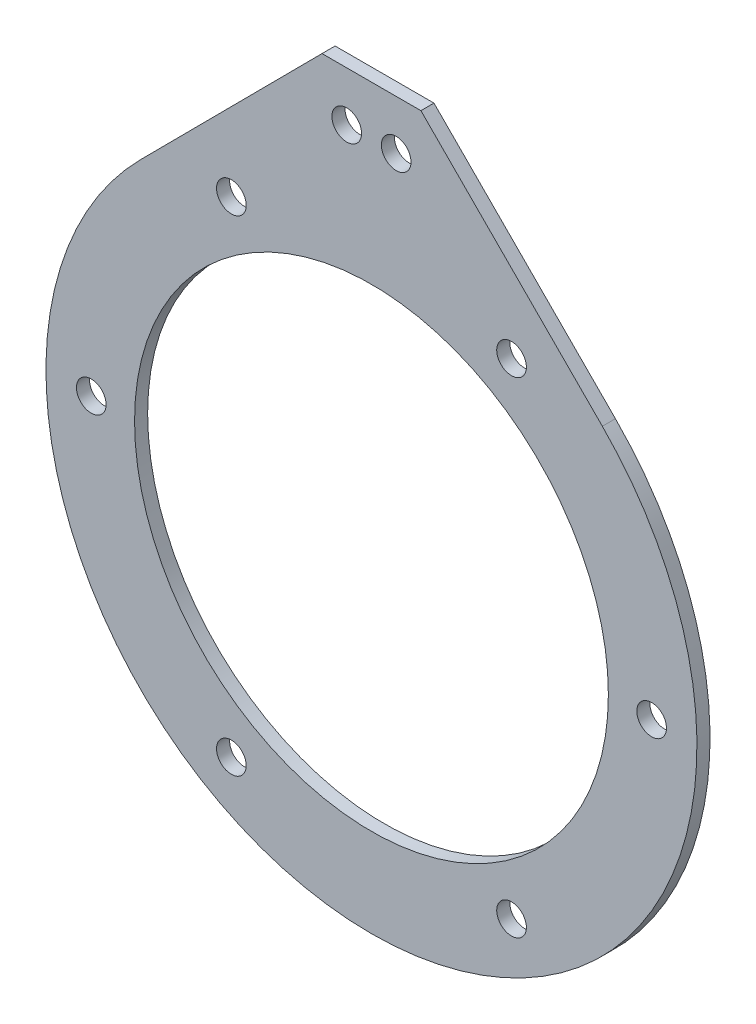
SolidWorks part; units mm, degrees
ref_plane "Front Plane" through (0, 0, 0) normal (0, 0, 1) x (1, 0, 0)
ref_plane "Top Plane" through (0, 0, 0) normal (0, 1, 0) x (1, 0, 0)
ref_plane "Right Plane" through (0, 0, 0) normal (1, 0, 0) x (0, 0, -1)
sketch "Sketch1" plane through (0, 0, 0) normal (0, 0, 1) x (1, 0, 0)
  circle A0 centre (0, 0) radius 39.5
  dimension "OuterDiam" = 79
extrude "Boss-Extrude1" add sketch "Sketch1" along normal mid plane 1.5875
sketch "Sketch3" plane through (0, 0, 0.7937) normal (0, 0, 1) x (1, 0, 0)
  line L0 (0, 50) -> (0, 0) construction
  line L2 (-28.0184, 27.8428) -> (-6, 50)
  line L3 (-6, 50) -> (6, 50)
  line L4 (28.0184, 27.8428) -> (6, 50)
  line L5 (-16.4342, 39.5) -> (16.4342, 39.5) construction
  line L6 (-28.0184, 27.8428) -> (28.0184, 27.8428)
  circle A1 centre (0, 0) radius 39.5 construction
  dimension "TopToHipAdductionCenter" = 10.5
  dimension "MotorCenterToAdductionCenter" = 39.5
  dimension "TopWidth" = 12
extrude "Boss-Extrude2" add sketch "Sketch3" against normal through all
sketch "Sketch4" plane through (0, 0, 0.7937) normal (0, 0, 1) x (1, 0, 0)
  line L0 (0, 50) -> (0, 0) construction
  line L1 (0, 47) -> (0, 32) construction
  line L2 (-16.4342, 39.5) -> (16.4342, 39.5) construction
  circle A0 centre (0, 47) radius 2.7
  circle A1 centre (0, 32) radius 2.7
  point P8 (0, 39.5)
  dimension "D2" = 5.4
  dimension "D1" = 15
extrude "Cut-Extrude2" [suppressed] cut sketch "Sketch4" against normal through all
sketch "Sketch2" plane through (0, 0, 0.7937) normal (0, 0, 1) x (1, 0, 0)
  circle A0 centre (0, 0) radius 28.75
  dimension "ElectronicsCutoutDiam" = 57.5
extrude "Cut-Extrude1" cut sketch "Sketch2" against normal through all
hole_wizard "M3 Clearance Hole1" positions "Sketch5" profile "Sketch6" hole size "M3" standard "ANSI Metric" end condition through all
sketch "Sketch5" plane through (0, 0, 0.7937) normal (0, 0, 1) x (1, 0, 0)
  line L7 (0, 0) -> (0, -28.75) construction
  line L10 (0, 0) -> (17, -29.4449) construction
  circle A1 centre (0, 0) radius 28.75 construction
  circle A2 centre (0, 0) radius 34 construction
  point P6 (17, -29.4449)
  dimension "MotorMountPatternDiam" = 68
  dimension "HoleAngleFromVert" = 30
sketch "Sketch6" plane through (17, -29.4449, 0.7937) normal (1, 0, 0) x (0, -1, 0)
  line L0 (0, 0) -> (0, 1.5875)
  line L1 (0, 1.5875) -> (1.8, 1.5875)
  line L2 (1.8, 1.5875) -> (1.8, 0)
  line L5 (1.8, 0) -> (0, 0)
  line L11 (0, -6.35) -> (0, 107.95) construction
  dimension "Thru Hole Dia." = 3.6
  dimension "Thru Hole Depth" = 1.5875
pattern_circular "CirPattern1" count 6 over 360 about axis through (0, 0, 0.7937) along (0, 0, 1) of "M3 Clearance Hole1"
hole_wizard "M3 Clearance Hole2" positions "Sketch7" profile "Sketch8" hole size "M3" standard "ANSI Metric"
sketch "Sketch7" plane through (0, 0, 0.7937) normal (0, 0, 1) x (1, 0, 0)
  line L0 (0, 50) -> (0, 39.5) construction
  line L1 (6, 50) -> (-6, 50) construction
  line L4 (-3, 44) -> (3, 44) construction
  line L5 (-6, 50) -> (6, 50) construction
  circle A0 centre (0, 0) radius 39.5 construction
  point P11 (-3, 44)
  point P12 (3, 44)
  point P17 (0, 44.75)
  point P21 (0, 44)
  dimension "D1" = 6
  dimension "D2" = 6
sketch "Sketch8" plane through (3, 44, 0.7937) normal (1, 0, 0) x (0, -1, 0)
  line L0 (0, 0) -> (0, 11.0815)
  line L1 (0, 11.0815) -> (1.8, 10)
  line L2 (1.8, 10) -> (1.8, 0)
  line L5 (1.8, 0) -> (0, 0)
  line L10 (0, 11.0815) -> (-1.8, 10) construction
  line L11 (0, -6.35) -> (0, 107.95) construction
  dimension "Hole Dia." = 3.6
  dimension "Hole Depth" = 10
  dimension "Drill Angle" = 118
sketch "OpenEdge" [suppressed] plane through (0, 0, -0.7937) normal (0, 0, -1) x (-1, 0, 0)
  line L0 (0, 0) -> (0, -38) construction
  line L1 (27.0162, 9.8331) -> (35.7083, 12.9968)
  line L2 (-22.0238, -18.4801) -> (-29.1097, -24.4259)
  circle A0 centre (0, 0) radius 38 construction
  circle A1 centre (0, 0) radius 28.75 construction
  circle A2 centre (0, 0) radius 28.75 construction
  arc A3 (-22.0238, -18.4801) -> (27.0162, 9.8331) centre (0, 0) ccw
  arc A4 (-29.1097, -24.4259) -> (35.7083, 12.9968) centre (0, 0) ccw
  dimension "frontAngle" = 110
  dimension "backAngle" = 50
extrude "Cut-Extrude3" [suppressed] cut sketch "OpenEdge" against normal through all
fillet "Fillet1" [suppressed] radius 3
ref_axis "Axis1" [suppressed] through (34, 0, -0.7937) along (0, 0, 1)
ref_axis "Axis2" [suppressed] through (17, 29.4449, -0.7937) along (0, 0, 1)
ref_axis "Axis3" [suppressed] through (-17, 29.4449, -0.7937) along (0, 0, 1)
ref_axis "Axis4" through (34, 0, -0.7937) along (0, 0, 1)
ref_axis "Axis5" through (17, 29.4449, -0.7937) along (0, 0, 1)
ref_axis "Axis6" through (-17, 29.4449, -0.7937) along (0, 0, 1)
ref_axis "Axis7" through (-34, 0, -0.7937) along (0, 0, 1)
ref_axis "Axis8" through (17, -29.4449, -0.7937) along (0, 0, 1)
ref_axis "Axis9" through (-17, -29.4449, -0.7937) along (0, 0, 1)
